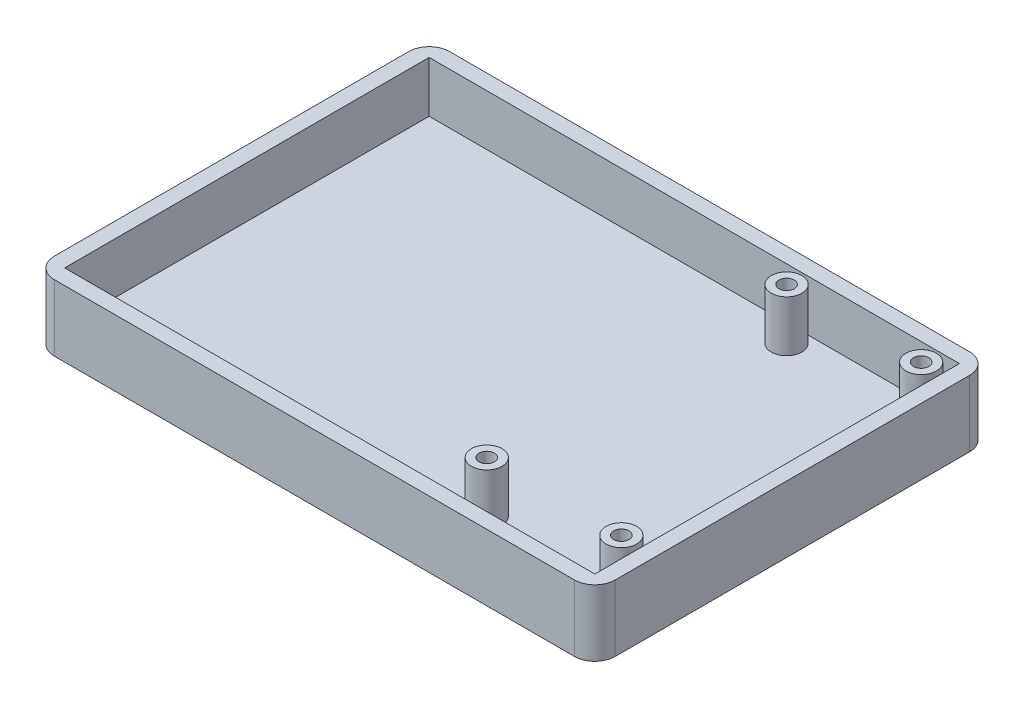
SolidWorks part; units mm, degrees
ref_plane "Front Plane" through (0, 0, 0) normal (0, 0, 1) x (1, 0, 0)
ref_plane "Top Plane" through (0, 0, 0) normal (0, 1, 0) x (1, 0, 0)
ref_plane "Right Plane" through (0, 0, 0) normal (1, 0, 0) x (0, 0, -1)
sketch "Sketch1" plane through (0, 0, 0) normal (0, 1, 0) x (1, 0, 0)
  line L0 (3, 74.5) -> (3, 3)
  line L1 (0, 77.5) -> (110, 77.5)
  line L2 (0, 77.5) -> (0, 0)
  line L3 (0, 0) -> (110, 0)
  line L4 (110, 77.5) -> (110, 0)
  line L5 (3, 3) -> (107, 3)
  line L6 (107, 74.5) -> (107, 3)
  line L7 (3, 74.5) -> (107, 74.5)
  line L8 (103, 71) -> (103, 12.2) construction
  circle A0 centre (76.6, 12.2) radius 1.5
  circle A1 centre (103, 12.2) radius 1.5
  circle A2 centre (76.6, 71) radius 1.5
  circle A3 centre (103, 71) radius 1.5
  circle A4 centre (76.6, 12.2) radius 3
  circle A5 centre (103, 12.2) radius 3
  circle A6 centre (103, 71) radius 3
  circle A7 centre (76.6, 71) radius 3
  point P8 (101.9485, 14.6876)
  point P17 (103, 66.3007)
  point P18 (0, 0)
  point P27 (-29.437, -56.9071)
  point P28 (0, 0)
  point P30 (102.5169, 7.1)
  point P31 (103.094, 7.1)
  dimension "D6" = 3
  dimension "D7" = 6
  dimension "D1" = 3
  dimension "D2" = 77.5
  dimension "D3" = 110
  dimension "D4" = 26.4
  dimension "D5" = 58.8
  dimension "D8" = 4
  dimension "D9" = 3.5
extrude "Boss-Extrude1" add sketch "Sketch1" along normal blind 10 contours L4 L1 L2 L3 L0 L7 L6 L5 | A5 A1 | A4 A0 | A7 A2 | A3 A6 region at (55, 0, -76.1544) region at (73.6849, 0, -12.2) region at (100.0849, 0, -12.2) region at (100.0849, 0, -71) region at (73.6849, 0, -71)
extrude "Boss-Extrude2" add sketch "Sketch1<2>" against normal blind 3 contours L7 L0 L5 L6 | L4 L1 L2 L3 L0 L7 L6 L5 | A4 A0 | A0 | A5 A1 | A1 | A7 A2 | A2 | A3 A6 | A3 region at (54.4625, 0, -38.706) region at (55, 0, -76.1544) region at (76.6, 0, -12.2) region at (103, 0, -12.2) region at (76.6, 0, -71) region at (103, 0, -71) region at (73.6849, 0, -12.2) region at (100.0849, 0, -12.2) region at (100.0849, 0, -71) region at (73.6849, 0, -71)
sketch "Sketch1<2>" plane through (0, 0, 0) normal (0, 1, 0) x (1, 0, 0) same geometry as "Sketch1"
fillet "Fillet1" radius 4 4 edges at (0, 3.5, -77.5) (0, 3.5, 0) (110, 3.5, -77.5) (110, 3.5, 0)
